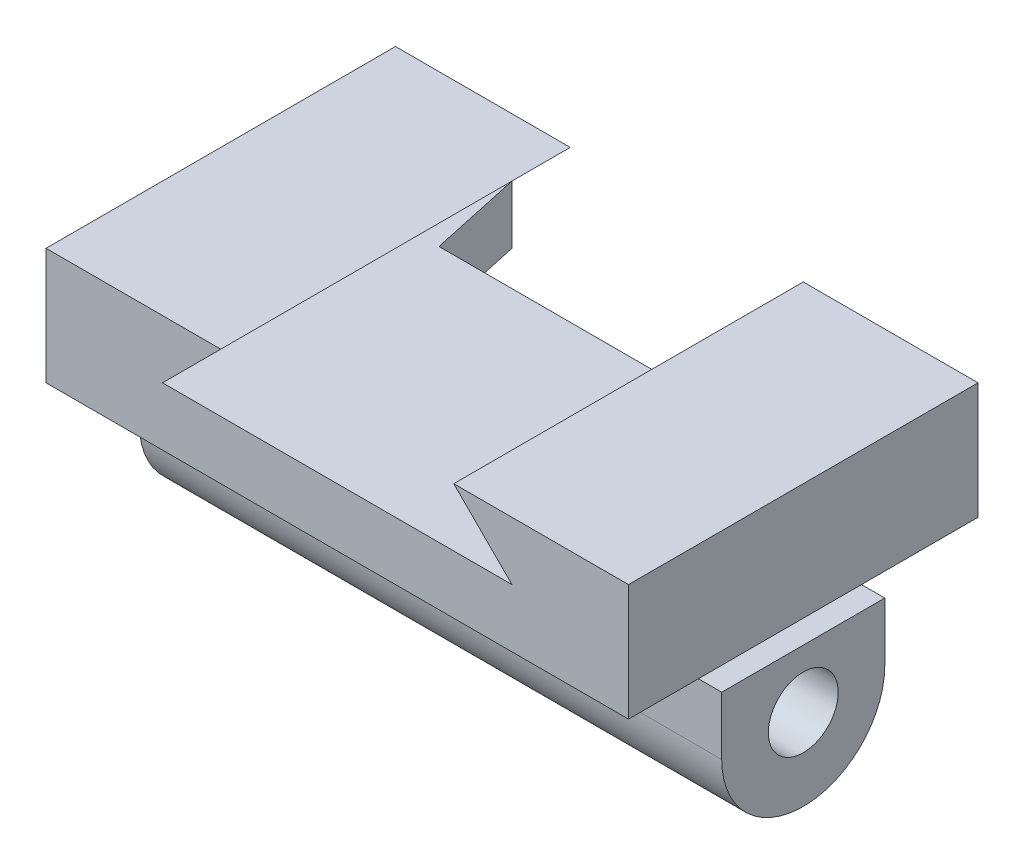
SolidWorks part; units mm, degrees
material "ABS PC"
ref_plane "Front Plane" through (0, 0, 0) normal (0, 0, 1) x (1, 0, 0)
ref_plane "Top Plane" through (0, 0, 0) normal (0, 1, 0) x (1, 0, 0)
ref_plane "Right Plane" through (0, 0, 0) normal (1, 0, 0) x (0, 0, -1)
sketch "Sketch1" plane through (0, 0, 0) normal (0, 1, 0) x (1, 0, 0)
  line L0 (0, 0) -> (0, 7) construction
  line L1 (-25, 15) -> (-15, 15)
  line L2 (-25, 15) -> (-25, -15)
  line L3 (-25, -15) -> (-15, -15)
  line L4 (-15, 15) -> (-15, -15)
  line L5 (-25, 15) -> (-15, -15) construction
  line L6 (-25, -15) -> (-15, 15) construction
  line L7 (25, -15) -> (15, 15) construction
  line L8 (25, 15) -> (15, -15) construction
  line L9 (15, 15) -> (15, -15)
  line L10 (25, -15) -> (15, -15)
  line L11 (25, 15) -> (25, -15)
  line L12 (25, 15) -> (15, 15)
  line L13 (-15, 15) -> (15, 15)
  line L22 (-15, -15) -> (15, -15)
  line L23 (-13.2665, 7) -> (13.2665, 7)
  line L24 (0, 0) -> (4.7808, 0) construction
  line L25 (-13.2665, -7) -> (13.2665, -7)
  line L26 (15, 15) -> (13.2665, 7)
  line L27 (-15, 15) -> (-13.2665, 7)
  circle A0 centre (0, 0) radius 15
  point P0 (-20, 0)
  point P12 (20, 0)
  point P17 (0, 7)
  dimension "D1" = 30
  dimension "D2" = 30
  dimension "D3" = 10
extrude "Boss-Extrude1" add sketch "Sketch1" along normal blind 5 contours L4 L1 L2 L3 | L11 L12 L9 L10 | A0 L22 L9 | A0 L25 | A0 L23 L25 | A0 L27 L4 | A0 L9 L26 | A0 L4 L22 region at (-20, 0, 0) region at (-14.4452, 0, -8.0723) region at (-11.6495, 0, 11.6495) region at (0, 0, 0) region at (0, 0, 10.2867) region at (20, 0, 0) region at (14.4452, 0, -8.0723) region at (11.6495, 0, 11.6495)
sketch "Sketch4" plane through (0, 0, 0) normal (0, -1, 0) x (1, 0, 0)
  line L0 (0, 0) -> (0, 7) construction
  line L1 (0, 0) -> (4.9545, 0) construction
  line L2 (-13.2665, 7) -> (13.2665, 7)
  line L3 (-13.2665, -7) -> (13.2665, -7)
  circle A0 centre (0, 0) radius 15
  point P8 (0, 7)
extrude "Boss-Extrude2" add sketch "Sketch4" along normal blind 2 contours L3 A0 L2 region at (0, 0, 0)
sketch "Sketch10" plane through (0, 0, 15) normal (0, 0, 1) x (1, 0, 0)
  line L0 (-15, 5) -> (-10, 10)
  line L1 (-25, 5) -> (-15, 5)
  line L2 (-25, 5) -> (-25, 10)
  line L3 (-25, 10) -> (-15, 10)
  line L4 (-15, 5) -> (-15, 10)
  line L5 (-10, 10) -> (-15, 10)
  line L6 (0, 5) -> (0, 10) construction
  line L7 (-25, 5) -> (25, 5) construction
  line L8 (10, 10) -> (15, 10)
  line L9 (15, 5) -> (15, 10)
  line L10 (25, 10) -> (15, 10)
  line L11 (25, 5) -> (25, 10)
  line L12 (25, 5) -> (15, 5)
  line L13 (15, 5) -> (10, 10)
  line M6 (25, 5) -> (-25, 5)
extrude "Boss-Extrude7" add sketch "Sketch10" against normal blind 30 contours L4 L3 L2 M6 | L0 L5 L4 | L13 L9 L8 | L11 L10 L9 M6 region at (-13.3333, 8.3333, 15) region at (-20, 7.5, 15) region at (13.3333, 8.3333, 15) region at (20, 7.5, 15)
sketch "Sketch11" plane through (25, 0, 0) normal (1, 0, 0) x (0, 0, -1)
  line L0 (0, 0) -> (0, -7) construction
  line L1 (15, 0) -> (-15, 0) construction
  line L2 (-7, -7) -> (-7, -2)
  line L3 (-7, -2) -> (7, -2)
  line L4 (7, -2) -> (7, -7)
  circle A0 centre (0, -7) radius 3
  arc A1 (-7, -7) -> (7, -7) centre (0, -7) ccw
extrude "Boss-Extrude8" add sketch "Sketch11" against normal blind 50
